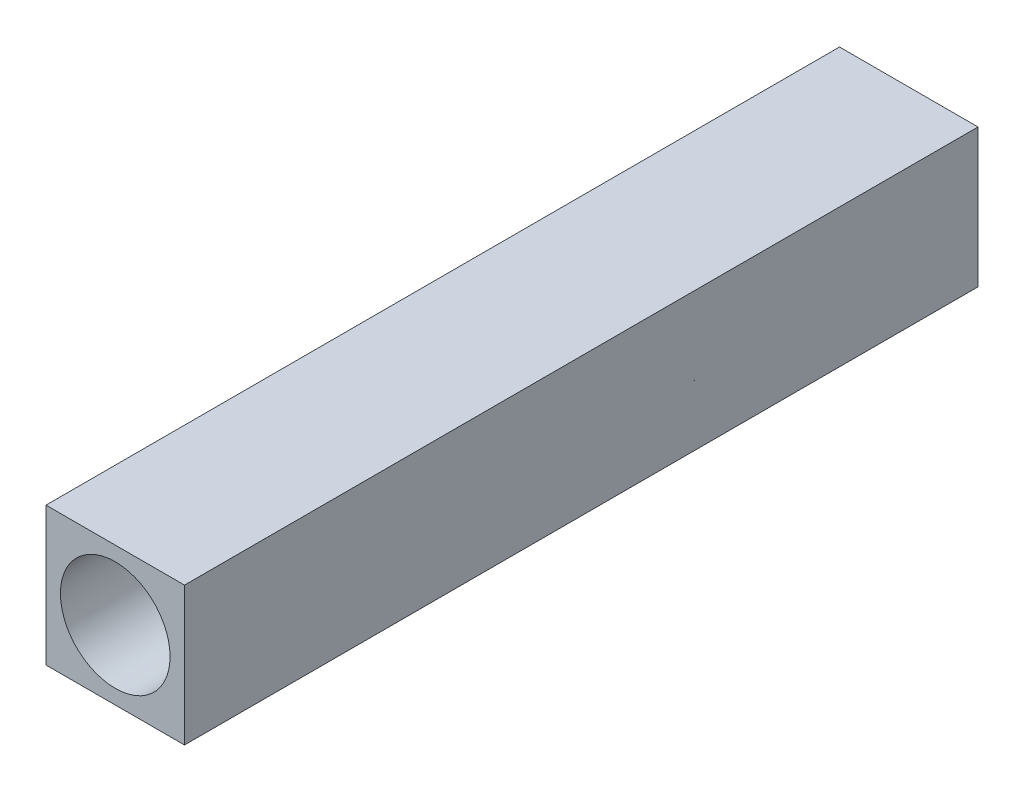
SolidWorks part; units mm, degrees
material "PET"
ref_plane "Front Plane" through (0, 0, 0) normal (0, 0, 1) x (1, 0, 0)
ref_plane "Top Plane" through (0, 0, 0) normal (0, 1, 0) x (1, 0, 0)
ref_plane "Right Plane" through (0, 0, 0) normal (1, 0, 0) x (0, 0, -1)
sketch "Sketch1" plane through (0, 0, 0) normal (0, 0, 1) x (1, 0, 0)
  circle A0 centre (0, 0) radius 9.652
  circle A1 centre (0, 0) radius 12.192
  dimension "D1" = 19.304
  dimension "D2" = 24.384
extrude "Main Inner Tube" add sketch "Sketch1" along normal blind 139.7
sketch "Sketch3" plane through (0, 0, 0) normal (0, 0, -1) x (-1, 0, 0)
  circle A0 centre (0, 0) radius 8.636
  circle A1 centre (0, 0) radius 9.652
  circle A2 centre (0, 0) radius 9.652 construction
  dimension "D1" = 17.272
extrude "Inner Blocking Lip" add sketch "Sketch3" against normal blind 6.35
sketch "Sketch6" plane through (0, 0, 139.7) normal (0, 0, 1) x (1, 0, 0)
  line L1 (-12.192, 12.192) -> (12.192, 12.192)
  line L2 (-12.192, 12.192) -> (-12.192, -12.192)
  line L3 (-12.192, -12.192) -> (12.192, -12.192)
  line L4 (12.192, 12.192) -> (12.192, -12.192)
  circle A0 centre (0, 0) radius 12.192 construction
  circle A1 centre (0, 0) radius 9.652
  circle A2 centre (0, 0) radius 9.652 construction
extrude "Rectangle Outside" add sketch "Sketch6" against normal through all
